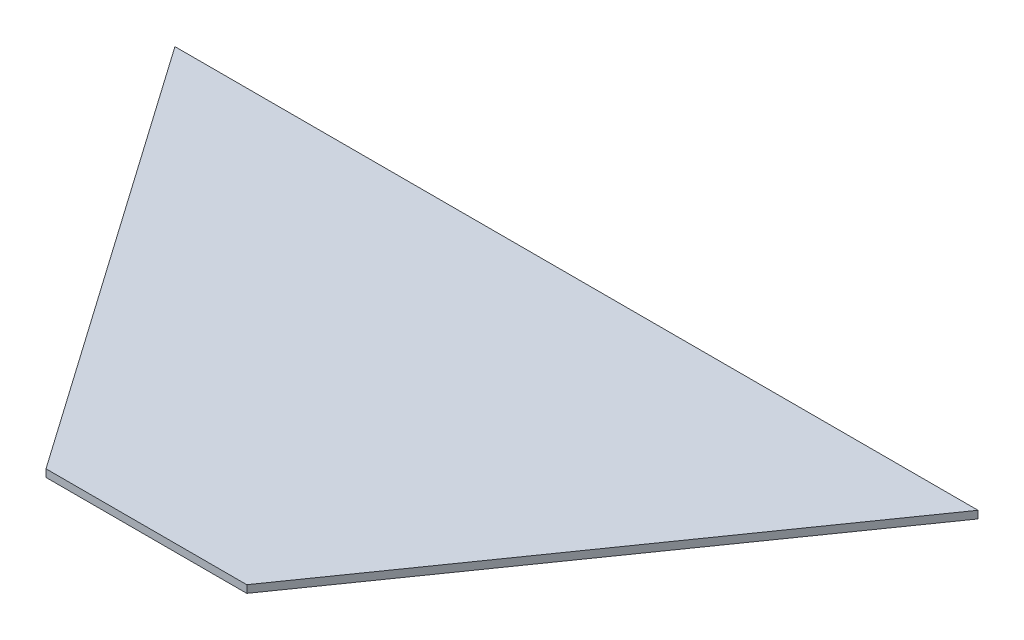
SolidWorks part; units mm, degrees
ref_plane "Front Plane" through (0, 0, 0) normal (0, 0, 1) x (1, 0, 0)
ref_plane "Top Plane" through (0, 0, 0) normal (0, 1, 0) x (1, 0, 0)
ref_plane "Right Plane" through (0, 0, 0) normal (1, 0, 0) x (0, 0, -1)
sketch "Sketch1" plane through (0, 0, 0) normal (0, 1, 0) x (1, 0, 0)
  line L0 (-80, 85.6889) -> (-20, 0)
  line L1 (80, 85.6889) -> (-80, 85.6889)
  line L3 (20, 0) -> (-20, 0)
  line L5 (80, 85.6889) -> (20, 0)
  dimension "D1" = 55
  dimension "D2" = 40
  dimension "D3" = 55
  dimension "D4" = 160
extrude "Boss-Extrude1" add sketch "Sketch1" along normal blind 1.5
equation "\"D4@Sketch1\"=\"D2@Sketch1\"*4"
equation "\"D3@Sketch1\"=\"D1@Sketch1\""
